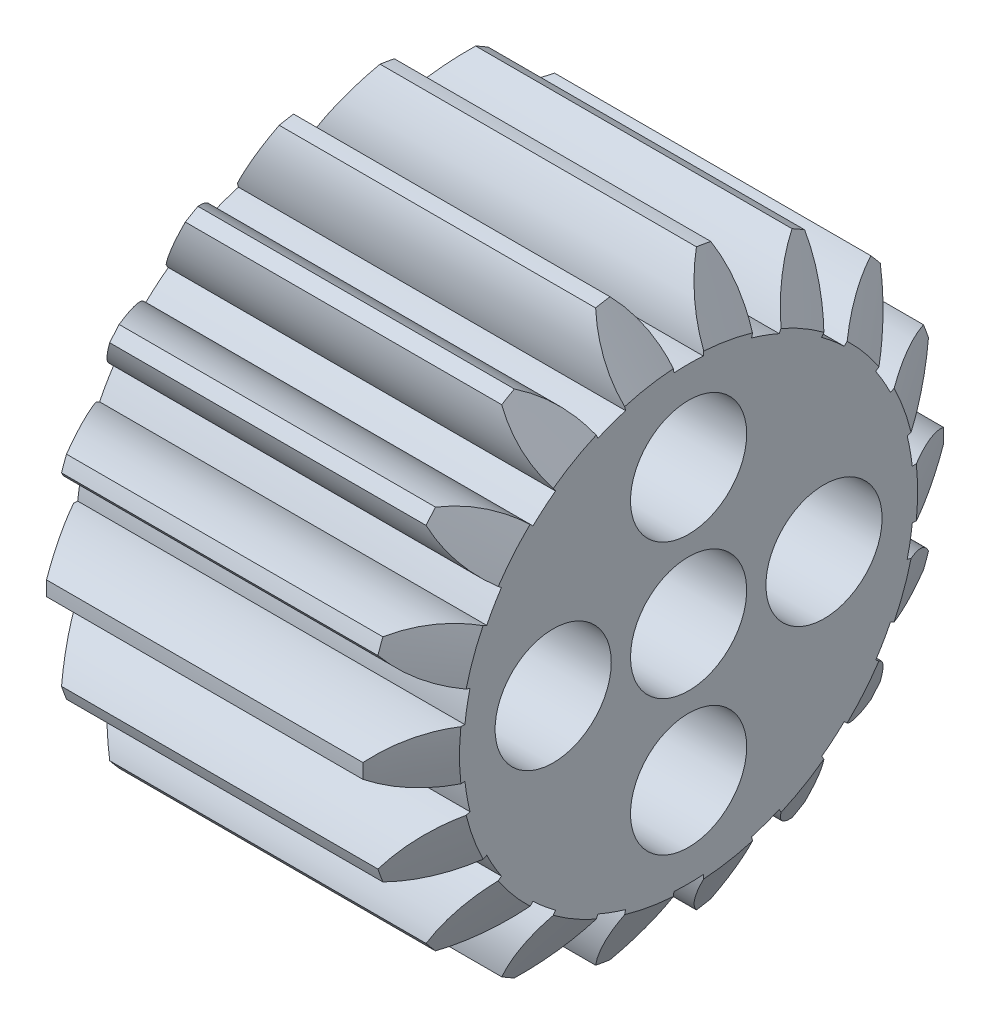
SolidWorks part; units mm, degrees
ref_plane "Plane1" through (0, 0, 0) normal (0, 0, 1) x (1, 0, 0)
ref_plane "Plane2" through (0, 0, 0) normal (0, 1, 0) x (1, 0, 0)
ref_plane "Plane3" through (0, 0, 0) normal (1, 0, 0) x (0, 0, -1)
other "Configuration Table"
sketch "HoldingSke" plane through (0, 0, 0) normal (0, 1, 0) x (1, 0, 0)
  line L0 (0, 0) -> (0.634, -0.206)
  line L1 (-15, 0) -> (100, 0) construction
  line L2 (0, 0) -> (-2.1039, 2.3779)
  line L3 (0, 0) -> (-11.863, 4.5341)
  line L4 (0, 0) -> (8.2133, 2.6687)
  line L5 (0, 0) -> (-46.8476, -17.4728)
  line L6 (0, 0) -> (-16.5793, -11.1861)
  line L7 (-2.1039, 2.3779) -> (8.6586, 51.2059)
  line L8 (-76.2, 54.61) -> (-75.2, 54.61)
  line L9 (-71.009, 38.7566) -> (-53.1078, 45.2721)
  line L10 (-76.2, 71.12) -> (104.1128, 71.12)
  line L11 (0, 0) -> (-20, 0)
  line L12 (-76.2, 101.6) -> (-76.147, 101.6)
  line L13 (24.9733, 27.94) -> (52.9518, 28.4284)
  line L14 (24.9733, 27.94) -> (24.9743, 27.94)
  line L15 (24.9733, 27.94) -> (100.4006, 29.5858)
  line L16 (-63.627, -1.5) -> (-12.827, -1.5)
  circle A0 centre (0, 0) radius 3
  circle A1 centre (0, 0) radius 11.624
  circle A2 centre (0, 0) radius 37.5
  circle A3 centre (0, 0) radius 3
  dimension "Num_teeth" = 18
  dimension "Pitch_radius" = 180.3128
  dimension "Width" = 20
  dimension "Thickness" = 20
sketch "BasProSke" plane through (0, 0, 0) normal (0, 1, 0) x (1, 0, 0)
  line L0 (-10, 0) -> (60, 0) construction
  line L1 (0, 0) -> (0, 15)
  line L2 (0, 0) -> (20, 0)
  line L3 (20, 0) -> (20, 15)
  line L4 (20, 15) -> (0, 15)
  dimension "Thickness" = 20
  dimension "Diameter" = 30
revolve "Base-Revolve" add sketch "BasProSke" angle 360 about L0
sketch "TooCutSke" plane through (0, 0, 0) normal (1, 0, 0) x (0, 0, -1)
  line L1 (0, 0) -> (0, 107) construction
  line L2 (0, 0) -> (-1.2693, 13.4402) construction
  line L3 (0, 0) -> (-4.6734, 26.504) construction
  line L4 (-1.2693, 13.4402) -> (-2.3367, 13.252) construction
  arc A0 (0.76, 11.5991) -> (-0.76, 11.5991) centre (0, 0) ccw
  arc A1 (2.2542, 14.8553) -> (-2.2542, 14.8553) centre (0, 0) ccw
  circle A2 centre (0, 0) radius 13.5 construction
  circle A3 centre (0, 0) radius 12.6859 construction
  arc A4 (-0.76, 11.5991) -> (-2.2542, 14.8553) centre (-6.1371, 11.1026) ccw
  arc A5 (2.2542, 14.8553) -> (0.76, 11.5991) centre (6.1371, 11.1026) ccw
extrude "ToothCut" cut sketch "TooCutSke" along normal through all
fillet "Breaks" [suppressed] radius 0.03 tangent propagation no
fillet "RootFillets" [suppressed] radius 0.376
pattern_circular "TeethCuts" count 18 every 20 about axis through (-10, 0, 0) along (1, 0, 0) of "ToothCut", "RootFillets", "Breaks"
sketch "HubNeaOneSke" plane through (0, 0, 0) normal (-1, 0, 0) x (0, 0, 1)
  circle A0 centre (0, 0) radius 11.624
  dimension "Diameter" = 23.248
extrude "HubNearOne" [suppressed] add sketch "HubNeaOneSke" along normal blind 30.0001
sketch "HubNeaBotSke" plane through (0, 0, 0) normal (-1, 0, 0) x (0, 0, 1)
  circle A0 centre (0, 0) radius 11.624
  dimension "Diameter" = 23.248
extrude "HubNearBoth" [suppressed] add sketch "HubNeaBotSke" along normal blind 15
ref_plane "FarPln" through (20, 0, 0) normal (1, 0, 0) x (0, 0, -1)
sketch "HubFarSke" plane through (20, 0, 0) normal (1, 0, 0) x (0, 0, -1)
  circle A0 centre (0, 0) radius 11.624
  dimension "Diameter" = 23.248
extrude "HubFar" [suppressed] add sketch "HubFarSke" along normal blind 15
sketch "BorSke" plane through (0, 0, 0) normal (1, 0, 0) x (0, 0, -1)
  circle A0 centre (0, 0) radius 3
  dimension "Diameter" = 6
extrude "Bore" cut sketch "BorSke" along normal mid plane 100.0001
sketch "KeySke" plane through (0, 0, 0) normal (1, 0, 0) x (0, 0, -1)
  line L0 (-1, 0) -> (-1, 4)
  line L1 (-1, 4) -> (1, 4)
  line L2 (1, 4) -> (1, 0)
  line L3 (0, 0) -> (0, 34) construction
  line L4 (-1, 0) -> (1, 0)
extrude "Keyway" [suppressed] cut sketch "KeySke" along normal mid plane 100.0001
pattern_circular "Keyway2" [suppressed] count 2 every 90 about axis through (-10, 0, 0) along (1, 0, 0)
sketch "Sketch1" plane through (20, 0, 0) normal (1, 0, 0) x (0, 0, -1)
  line L0 (0, 7) -> (0, -7) construction
  circle A0 centre (6.9946, -0.2738) radius 1.75
  circle A1 centre (-6.9946, 0.2738) radius 1.75
  circle A2 centre (0, 0) radius 7 construction
  circle A3 centre (0, 7) radius 1.75
  circle A4 centre (0, -7) radius 1.75
  circle A5 centre (0, -7) radius 3
  circle A6 centre (6.9946, -0.2738) radius 3
  circle A7 centre (0, 7) radius 3
  circle A8 centre (-6.9946, 0.2738) radius 3
  dimension "D1" = 3.5
  dimension "D2" = 6
extrude "Cut-Extrude1" cut sketch "Sketch1" against normal blind 20 contours A1 | A3 | A0 | A4 region at (20, -0.2738, -6.9946) region at (20, 0.2738, 6.9946) region at (20, 7, 0) region at (20, -7, 0)
extrude "Cut-Extrude3" cut sketch "Sketch1<5>" against normal blind 15
sketch "Sketch1<5>" plane through (20, 0, 0) normal (1, 0, 0) x (0, 0, -1) same geometry as "Sketch1"
sketch "Sketch2" plane through (0, 0, 0) normal (0, 0, -1) x (1, 0, 0)
  line L0 (0, 15.0329) -> (1.8475, 15.0329)
  line L2 (1.8475, 15.0329) -> (0, 11.8329)
  line L4 (0, 11.8329) -> (0, 15.0329)
  line L6 (0, 11.624) -> (0, 11.5991) construction
  line L7 (0, 14.8329) -> (20, 14.8329) construction
  line L8 (10, 14.8329) -> (10, -14.702) construction
  line L9 (0, -14.702) -> (20, -14.702) construction
  line L10 (20, 11.8329) -> (20, 15.0329)
  line L11 (18.1525, 15.0329) -> (20, 11.8329)
  line L12 (20, 15.0329) -> (18.1525, 15.0329)
  line L13 (0, 0) -> (19.221, 0) construction
  point P11 (0, 14.8329)
  point P12 (0, 14.8372)
  point P13 (1.8475, 14.9187)
  point P14 (0, 14.9821)
  dimension "D1" = 30
  dimension "D2" = 3.2
  dimension "D3" = 0.2
revolve "Cut-Revolve1" cut sketch "Sketch2" angle 360 about L13
equation "' \"Module@HoldingSke\" = 6.35"
equation "' \"Num_teeth@HoldingSke\" = 12"
equation "' \"Ap@HoldingSke\" =  20"
equation "' \"Ap@HoldingSke\" = 20"
equation "' \"Width@HoldingSke\" = 0.5 * 25.4"
equation "' \"Hub_dia@HoldingSke\"= 1 * 25.4"
equation "' \"Hub_dia@HoldingSke\" = 1 * 25.4"
equation "' \"Overall_len@HoldingSke\" = 1.0 * 25.4"
equation "' \"Bore@HoldingSke\" = 0.75 * 25.4"
equation "' \"T_dim@HoldingSke\" = 0.1 * 25.4"
equation "' \"Width@KeySke\" = 0.25 * 25.4"
equation "' \"Show_teeth@HoldingSke\" = 13"
equation "' \"Backlash@HoldingSke\" = 0.009 * 25.4"
equation "' \"Addendum_fac@HoldingSke\" = 1.0"
equation "' \"Dedendum_fac@HoldingSke\" = 1.25"
equation "' \"Dedendum_add@HoldingSke\" = 0.00005 * 25.4"
equation "' \"Clearance_fac@HoldingSke\" = 0.25"
equation "\"Pitch@HoldingSke\" = 1 / \"Module@HoldingSke\""
equation "\"Overcut_dia@TooCutSke\" = (\"Num_teeth@HoldingSke\" + 2 * \"Addendum_fac@HoldingSke\") / \"Pitch@HoldingSke\" + 0.002 * 25.4"
equation "\"Pitch_dia@TooCutSke\" = \"Num_teeth@HoldingSke\" / \"Pitch@HoldingSke\""
equation "\"Base_dia@TooCutSke\" = \"Num_teeth@HoldingSke\" / \"Pitch@HoldingSke\" * cos((\"Ap@HoldingSke\"  * 3.14159265 / 180))"
equation "\"Root_dia@TooCutSke\" = (\"Num_teeth@HoldingSke\" + 2) / \"Pitch@HoldingSke\" - 2 * (\"Addendum_fac@HoldingSke\" + \"Dedendum_fac@HoldingSke\") / \"Pitch@HoldingSke\" - \"Dedendum_add@HoldingSke\" * 2"
equation "\"Half_ang@TooCutSke\" = 180 / \"Num_teeth@HoldingSke\""
equation "\"Half_CT@TooCutSke\" = \"Num_teeth@HoldingSke\" / \"Pitch@HoldingSke\" * sin((3.14159265 / 2 / \"Num_teeth@HoldingSke\")) / 2 - 7 * \"Backlash@HoldingSke\" / 4"
equation "\"Flank_rad@TooCutSke\" = \"Num_teeth@HoldingSke\" / \"Pitch@HoldingSke\" / 5"
equation "\"Radius@RootFillets\" = \"Clearance_fac@HoldingSke\" / \"Pitch@HoldingSke\" + \"Dedendum_add@HoldingSke\""
equation "\"Break_rad@Breaks\" = 0.02 / \"Pitch@HoldingSke\""
equation "\"Thickness@HoldingSke\" = \"Width@HoldingSke\""
equation "\"OAL@HoldingSke\" = \"Thickness@HoldingSke\""
equation "\"MHD@HoldingSke\" = (\"Num_teeth@HoldingSke\" + 2) / \"Pitch@HoldingSke\" - 2 * (\"Addendum_fac@HoldingSke\" + \"Dedendum_fac@HoldingSke\")  / \"Pitch@HoldingSke\" - \"Dedendum_add@HoldingSke\" * 2"
equation "\"MBD@HoldingSke\" = (\"Num_teeth@HoldingSke\" + 2) / \"Pitch@HoldingSke\" - 2 * (\"Addendum_fac@HoldingSke\" + \"Dedendum_fac@HoldingSke\")  / \"Pitch@HoldingSke\" - \"Dedendum_add@HoldingSke\" * 2 - 0.002 * 25.4"
equation "\"MHD@HoldingSke\" = ((sgn( \"MHD@HoldingSke\" - \"Hub_dia@HoldingSke\" )-1)*( \"MHD@HoldingSke\" - \"Hub_dia@HoldingSke\" ))/-2+ \"Hub_dia@HoldingSke\""
equation "\"MBD@HoldingSke\" = ((sgn( \"MBD@HoldingSke\" - \"Bore@HoldingSke\" )-1)*( \"MBD@HoldingSke\" - \"Bore@HoldingSke\" ))/-2+ \"Bore@HoldingSke\""
equation "\"OAL@HoldingSke\" = ((sgn( \"OAL@HoldingSke\" - \"Overall_len@HoldingSke\" )+1)*( \"OAL@HoldingSke\" - \"Overall_len@HoldingSke\" ))/2 + \"Overall_len@HoldingSke\" + 0.000002 * 25.4"
equation "\"Num_teeth@TeethCuts\" = int( \"Show_teeth@HoldingSke\" ) + 1"
equation "\"Num_teeth@TeethCuts\" = ((sgn( \"Num_teeth@TeethCuts\" - \"Num_teeth@HoldingSke\" )-1)*( \"Num_teeth@TeethCuts\" - \"Num_teeth@HoldingSke\" ))/-2+ \"Num_teeth@HoldingSke\""
equation "\"Num_teeth@TeethCuts\" = ((sgn( \"Num_teeth@TeethCuts\" - 2.0)+1)*( \"Num_teeth@TeethCuts\" - 2.0))/2 +2.0"
equation "\"Angle@TeethCuts\" = 360.0 / \"Num_teeth@HoldingSke\""
equation "\"Diameter@BasProSke\" = (\"Num_teeth@HoldingSke\" + 2 * \"Addendum_fac@HoldingSke\") / \"Pitch@HoldingSke\""
equation "\"Thickness@BasProSke\"  = \"Thickness@HoldingSke\""
equation "' \"Fillet_rad@BasProSke\" =  \"Thickness@HoldingSke\" * 0.05"
equation "' \"Fillet_rad@BasProSke\" = \"Thickness@HoldingSke\" * 0.05"
equation "\"MHD@HoldingSke\" = ((sgn( \"MHD@HoldingSke\" - \"Root_dia@TooCutSke\" )-1)*( \"MHD@HoldingSke\" - \"Root_dia@TooCutSke\" ))/-2+ \"Root_dia@TooCutSke\""
equation "\"Diameter@HubNeaOneSke\" = \"MHD@HoldingSke\""
equation "\"Length@HubNearOne\" = \"OAL@HoldingSke\" - \"Thickness@BasProSke\""
equation "\"Diameter@HubNeaBotSke\" = \"MHD@HoldingSke\""
equation "\"Length@HubNearBoth\" = ( \"OAL@HoldingSke\" - \"Thickness@BasProSke\" ) / 2.0"
equation "\"Thickness@FarPln\" = \"Thickness@BasProSke\""
equation "\"Diameter@HubFarSke\" = \"MHD@HoldingSke\""
equation "\"Length@HubFar\" = ( \"OAL@HoldingSke\" - \"Thickness@BasProSke\" ) / 2.0"
equation "\"Diameter@BorSke\" = \"MBD@HoldingSke\""
equation "\"D1@Bore\" = \"OAL@HoldingSke\" * 2.0"
equation "\"D1@Keyway\" = \"OAL@HoldingSke\" * 2.0"
equation "\"Offset@KeySke\" = \"T_dim@HoldingSke\" + \"MBD@HoldingSke\" / 2.0"
